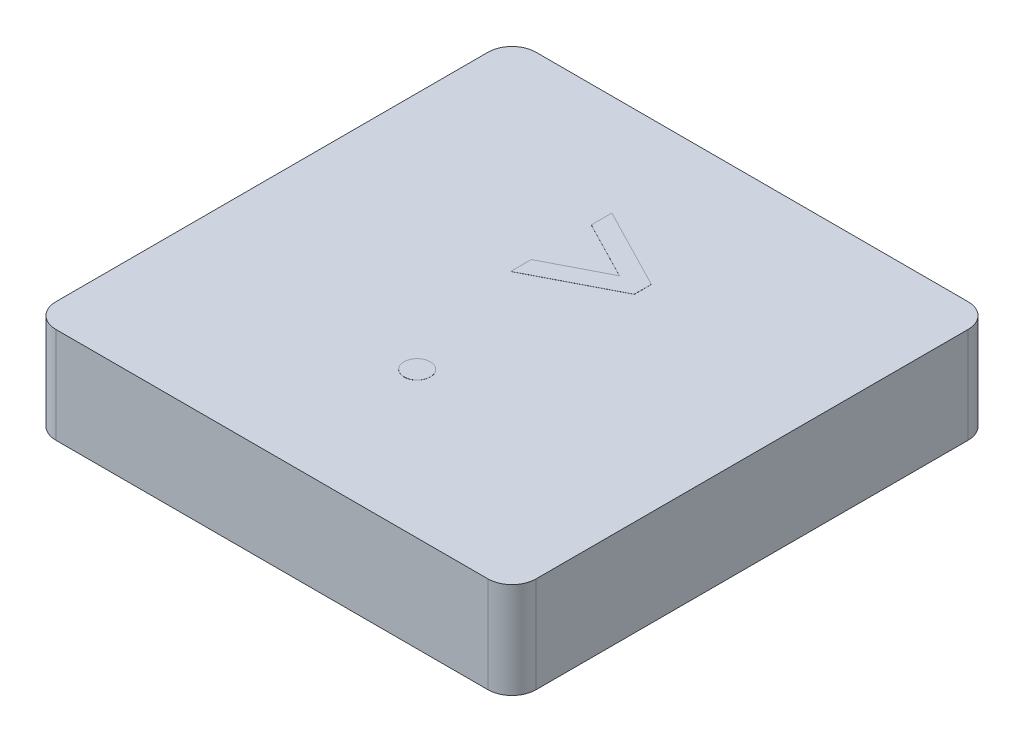
SolidWorks part; units mm, degrees
ref_plane "Front Plane" through (0, 0, 0) normal (0, 0, 1) x (1, 0, 0)
ref_plane "Top Plane" through (0, 0, 0) normal (0, 1, 0) x (1, 0, 0)
ref_plane "Right Plane" through (0, 0, 0) normal (1, 0, 0) x (0, 0, -1)
sketch "Sketch1" plane through (0, 0, 0) normal (0, 1, 0) x (1, 0, 0)
  line L0 (0, 0) -> (12.7, 0)
  line L1 (12.7, 0) -> (12.7, 12.7)
  line L2 (12.7, 12.7) -> (0, 12.7)
  line L3 (0, 12.7) -> (0, 0)
  dimension "D1" = 12.7
  dimension "D2" = 12.7
extrude "Boss-Extrude1" add sketch "Sketch1" along normal blind 2.54
fillet "Fillet1" radius 0.635 4 edges at (0, 1.27, -12.7) (12.7, 1.27, -12.7) (12.7, 1.27, 0) (0, 1.27, 0)
shell "Shell1" thickness 0.635 removed face at (6.35, 0, -6.35)
sketch "Sketch2" plane through (0, 1.905, 0) normal (0, -1, 0) x (-1, 0, 0)
  line L0 (-0.635, 6.35) -> (-12.065, 6.35) construction
  line L1 (-0.635, 12.065) -> (-0.635, 0.635) construction
  line L2 (-12.065, 0.635) -> (-12.065, 12.065) construction
  line L3 (-6.35, 0.635) -> (-6.35, 12.065) construction
  line L4 (-0.635, 0.635) -> (-12.065, 0.635) construction
  line L5 (-12.065, 12.065) -> (-0.635, 12.065) construction
  circle A0 centre (-6.35, 6.35) radius 2.54
  dimension "D1" = 5.08
extrude "Boss-Extrude2" add sketch "Sketch2" along normal up to surface (1.905 mm away) up to face at (6.35, 0, -6.35)
sketch "Sketch3" plane through (0, 2.54, 0) normal (0, 1, 0) x (1, 0, 0)
  line L0 (0.635, 0) -> (12.065, 0) construction
  line L1 (0, 12.065) -> (0, 0.635) construction
  line L2 (12.065, 12.7) -> (0.635, 12.7) construction
  text T0 "<b>></b>"
  text T1 "<b>.</b>"
  dimension "D1" = 3.556
  dimension "D2" = 5.7404
  dimension "D3" = 5.588
  dimension "D4" = 5.08
extrude "Boss-Extrude3" add sketch "Sketch3" along normal blind 0.0025
